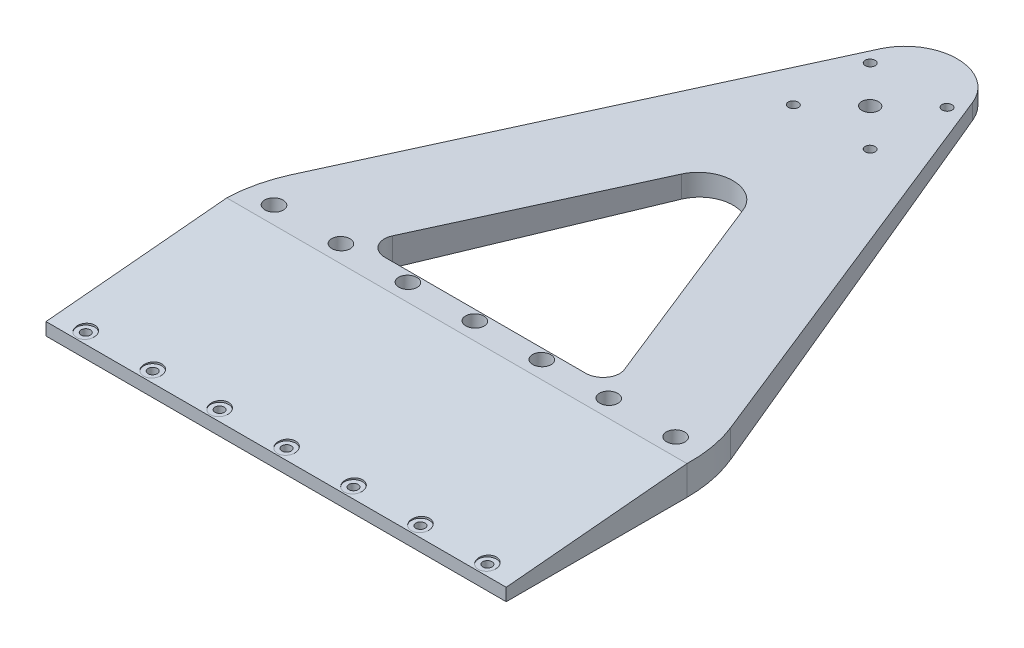
SolidWorks part; units mm, degrees
ref_plane "Front Plane" through (0, 0, 0) normal (0, 0, 1) x (1, 0, 0)
ref_plane "Top Plane" through (0, 0, 0) normal (0, 1, 0) x (1, 0, 0)
ref_plane "Right Plane" through (0, 0, 0) normal (1, 0, 0) x (0, 0, -1)
sketch "Sketch1" plane through (0, 0, 0) normal (0, 1, 0) x (1, 0, 0)
  line L1 (0, 0) -> (139.7, 0)
  line L2 (0, 0) -> (0, 63.5)
  line L3 (0, 63.5) -> (139.7, 63.5)
  line L4 (139.7, 0) -> (139.7, 63.5)
  dimension "D1" = 63.5
  dimension "D2" = 139.7
extrude "Boss-Extrude1" add sketch "Sketch1" along normal blind 8.89
sketch "Sketch2" plane through (0, 8.89, 0) normal (0, 1, 0) x (1, 0, 0)
  line L0 (139.7, 0) -> (139.7, 3.175) construction
  line L1 (139.7, 0) -> (139.7, 63.5) construction
  line L2 (139.7, 3.175) -> (0, 3.175) construction
  line L3 (0, 63.5) -> (0, 0) construction
  line L4 (139.7, 60.325) -> (0, 60.325) construction
  line L5 (0, 0) -> (139.7, 0) construction
  line L6 (139.7, 63.5) -> (0, 63.5) construction
  circle A0 centre (69.85, 60.325) radius 1.4
  circle A1 centre (69.85, 3.175) radius 1.4
  circle A2 centre (90.17, 3.175) radius 1.4
  circle A3 centre (110.49, 3.175) radius 1.4
  circle A4 centre (130.81, 3.175) radius 1.4
  circle A5 centre (49.53, 3.175) radius 1.4
  circle A6 centre (29.21, 3.175) radius 1.4
  circle A7 centre (8.89, 3.175) radius 1.4
  circle A8 centre (90.17, 60.325) radius 1.4
  circle A9 centre (110.49, 60.325) radius 1.4
  circle A10 centre (130.81, 60.325) radius 1.4
  circle A11 centre (49.53, 60.325) radius 1.4
  circle A12 centre (29.21, 60.325) radius 1.4
  circle A13 centre (8.89, 60.325) radius 1.4
  dimension "D3" = 2.8
  dimension "D4" = 2.8
  dimension "D1" = 3.175
  dimension "D2" = 3.175
  dimension "D5" = 4
  dimension "D6" = 4
  dimension "D7" = 4
  dimension "D8" = 4
extrude "Cut-Extrude1" cut sketch "Sketch2" against normal blind 16.51
sketch "Sketch3" plane through (0, 8.89, 0) normal (0, 1, 0) x (1, 0, 0)
  line L0 (69.85, 63.5) -> (69.85, 231.14) construction
  line L1 (139.7, 63.5) -> (0, 63.5) construction
  line L2 (55.7823, 197.3775) -> (0, 63.5)
  line L3 (0, 63.5) -> (139.7, 63.5)
  line L4 (139.7, 63.5) -> (83.9177, 197.3775)
  line L5 (69.85, 63.5) -> (31.75, 63.5)
  line L6 (31.75, 63.5) -> (69.85, 154.94)
  line L7 (69.85, 154.94) -> (107.95, 63.5)
  circle A0 centre (69.85, 180.34) radius 12.2845
  arc A1 (55.7823, 197.3775) -> (83.9177, 197.3775) centre (69.85, 191.516) cw
  point P16 (0, 0)
  point P17 (0, 0)
  point P18 (69.85, 160.6098)
  line M22 (139.7, 63.5) -> (0, 63.5)
  dimension "D3" = 15.24
  dimension "D1" = 116.84
  dimension "D2" = 50.8
  dimension "D4" = 31.75
  dimension "D5" = 31.75
  dimension "D6" = 0
extrude "Boss-Extrude2" add sketch "Sketch3" against normal blind 8.89 separate body contours L0 L7 L4 A1 A0 M22 | L6 L0 A0 A1 L2 M22 | A0 L0 | L0 A0 region at (39.7511, 8.89, -123.7736) region at (99.9489, 8.89, -123.7736) region at (64.6363, 8.89, -180.34) region at (75.0637, 8.89, -180.34)
fillet "Fillet1" radius 10.16 1 edges at (69.85, 4.445, -154.94)
combine bodies "Combine1" operation type add bodies to combine 102 103
fillet "Fillet2" radius 5.08 2 edges at (31.75, 4.445, -63.5) (107.95, 4.445, -63.5)
fillet "Fillet3" radius 43.18 2 edges at (0, 4.445, -63.5) (139.7, 4.445, -63.5)
sketch "Sketch4" plane through (0, 8.89, 0) normal (0, 1, 0) x (1, 0, 0)
  line L0 (69.85, 63.5) -> (69.85, 206.756) construction
  line L5 (100.33, 63.5) -> (39.37, 63.5) construction
  line L6 (57.1221, 167.6121) -> (59.2434, 169.7334) construction
  line L8 (82.5779, 193.0679) -> (57.1221, 167.6121) construction
  circle A0 centre (69.85, 180.34) radius 18
  arc A1 (83.9177, 197.3775) -> (55.7823, 197.3775) centre (69.85, 191.516) ccw construction
  circle A2 centre (69.85, 180.34) radius 15
  circle A3 centre (58.1827, 168.6727) radius 1.5
  circle A4 centre (58.1827, 192.0073) radius 1.5
  circle A5 centre (81.5173, 192.0073) radius 1.5
  circle A6 centre (81.5173, 168.6727) radius 1.5
  circle A7 centre (69.85, 180.34) radius 2.5
  point P24 (69.85, 180.34)
  dimension "D1" = 36
  dimension "D2" = 30
  dimension "D5" = 5
  dimension "D3" = 116.84
  dimension "D4" = 4
extrude "Cut-Extrude3" cut sketch "Sketch4" against normal blind 11.43 contours A3 | A7 | A5 | A4 | A6 region at (81.5173, 8.89, -192.0073) region at (81.5173, 8.89, -168.6727) region at (58.1827, 8.89, -192.0073) region at (58.1827, 8.89, -168.6727) region at (69.85, 8.89, -180.34)
sketch "Sketch20" plane through (0, 0, 0) normal (-1, 0, 0) x (0, 0, 1)
  line L0 (0, 0) -> (0, 3.81)
  line L1 (0, 8.89) -> (0, 0) construction
  line L2 (0, 3.81) -> (-54.864, 8.89)
  line L3 (-54.864, 8.89) -> (-206.756, 4.445)
  line L4 (-206.756, 8.89) -> (-206.756, 0) construction
  line L5 (-206.756, 4.445) -> (0, 3.81)
  line L6 (-206.756, 4.445) -> (-206.756, 8.89)
  line L7 (-206.756, 4.445) -> (-206.6259, 0)
  line L8 (-206.756, 0) -> (-197.3775, 0) construction
  line L9 (-206.756, 8.89) -> (-54.864, 8.89)
  line L10 (0, 8.89) -> (0, 3.81)
  line M3 (0, 8.89) -> (-54.864, 8.89)
  line M6 (0, 0) -> (0, 8.89)
  dimension "D1" = 3.81
extrude "Cut-Extrude6" cut sketch "Sketch20" against normal blind 198.882 contours L9 L6 L3 | L2 M6 M3 region at (0, 7.1967, -18.288) region at (0, 7.4083, -156.1253)
ref_plane "Plane4" through (0, 0, -206.756) normal (0, 0, -1) x (-1, 0, 0)
ref_axis "Axis3" through (0, -0.4445, -206.756) along (0, 1, 0)
sketch "Sketch22" plane through (0, 10.4866, -0.3069) normal (0, 0.9996, -0.0293) x (1, 0, 0)
  circle A0 centre (130.81, 60.0438) radius 2.75
  circle A1 centre (110.49, 60.0438) radius 2.75
  circle A2 centre (90.17, 60.0438) radius 2.75
  circle A3 centre (69.85, 60.0438) radius 2.75
  circle A4 centre (49.53, 60.0438) radius 2.75
  circle A5 centre (29.21, 60.0438) radius 2.75
  circle A6 centre (8.89, 60.0438) radius 2.75
  dimension "D2" = 5.5
  dimension "D1" = 7
extrude "Cut-Extrude8" cut sketch "Sketch22" against normal blind 4.572
ref_plane "Plane5" through (0, 3.81, 0) normal (0, -1, 0) x (-1, 0, 0)
sketch "Sketch23" plane through (0, 3.81, 0) normal (0, -1, 0) x (-1, 0, 0)
  circle A0 centre (-8.89, 3.175) radius 2.75
  circle A1 centre (-29.21, 3.175) radius 2.75
  circle A2 centre (-49.53, 3.175) radius 2.75
  circle A3 centre (-69.85, 3.175) radius 2.75
  circle A4 centre (-90.17, 3.175) radius 2.75
  circle A5 centre (-110.49, 3.175) radius 2.75
  circle A6 centre (-130.81, 3.175) radius 2.75
  dimension "D1" = 5.5
  dimension "D2" = 7
extrude "Cut-Extrude9" cut sketch "Sketch23" against normal blind 4.572
